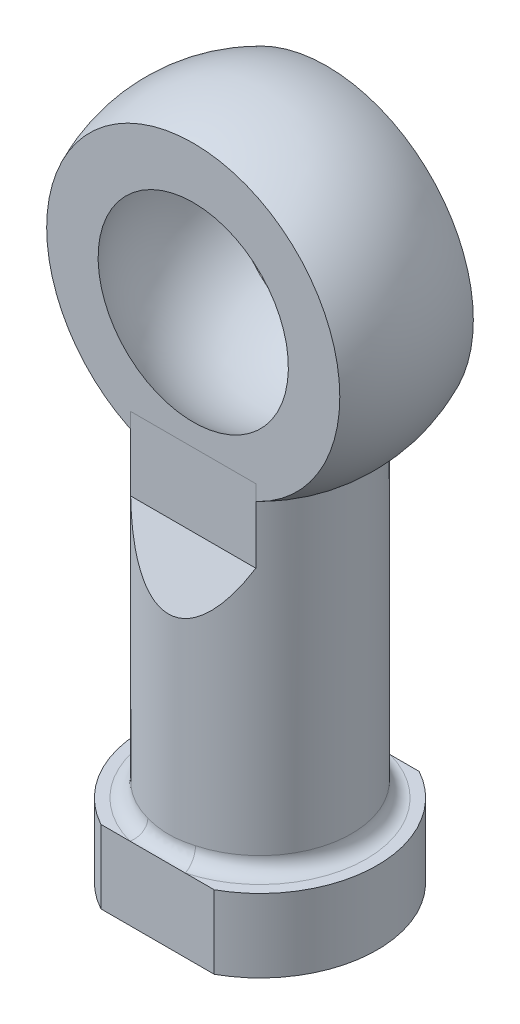
SolidWorks part; units mm, degrees
material "Plain Carbon Steel"
ref_plane "Front Plane" through (0, 0, 0) normal (0, 0, 1) x (1, 0, 0)
ref_plane "Top Plane" through (0, 0, 0) normal (0, 1, 0) x (1, 0, 0)
ref_plane "Right Plane" through (0, 0, 0) normal (1, 0, 0) x (0, 0, -1)
sketch "Sketch2" plane through (0, 0, 0) normal (1, 0, 0) x (0, 0, -1)
  line L0 (0, 15.4744) -> (0, -15.7624) construction
  line L1 (0, 7.938) -> (0, -7.938)
  arc A0 (0, 7.938) -> (0, -7.938) centre (0, 0) cw
  point P6 (0, -14.2606)
  dimension "D1" = 7.938
sketch "Sketch3" plane through (0, 0, 0) normal (1, 0, 0) x (0, 0, -1)
  line L0 (-8.1466, 0) -> (8.1466, 0) construction
  line L1 (0, 31.115) -> (0, -31.115) construction
  line L2 (-4.56, 10.0103) -> (-4.56, 0)
  line L3 (-4.56, 0) -> (4.56, 0)
  line L4 (4.56, 0) -> (4.56, 10.0103)
  arc A0 (-4.56, 10.0103) -> (4.56, 10.0103) centre (0, 0) cw
  point P8 (0, 11)
  dimension "D2" = 9.12
  dimension "D1" = 11
revolve "Revolve2" add sketch "Sketch3"
revolve "Cut-Revolve2" cut sketch "Sketch2" angle 360 about L0
sketch "Sketch4" plane through (0, 0, 0) normal (1, 0, 0) x (0, 0, -1)
  line L0 (0, -11) -> (0, -35.6534) construction
  arc A0 (-4.56, -10.0103) -> (4.56, -10.0103) centre (0, 0) ccw construction
ref_plane "Plane1" through (0, -11, 0) normal (0, 1, 0) x (-1, 0, 0)
sketch "Sketch5" plane through (0, -11, 0) normal (0, 1, 0) x (-1, 0, 0)
  circle A0 centre (0, 0) radius 6.25
  circle A1 centre (0, 0) radius 3.4
  dimension "D1" = 12.5
  dimension "D2" = 6.8
extrude "Extrude2" add sketch "Sketch5" against normal blind 25 and the other way blind 3 separate body
cosmetic thread "Cosmetic Thread1" parameters "D1"=29, "D2"=8
sketch "Sketch7" plane through (0, -36, 0) normal (0, -1, 0) x (1, 0, 0)
  line L0 (-3.873, 7) -> (3.873, 7)
  line L1 (-3.873, -7) -> (3.873, -7)
  circle A0 centre (0, 0) radius 3.4 construction
  circle A1 centre (0, 0) radius 3.4
  arc A2 (-3.873, 7) -> (-3.873, -7) centre (0, 0) ccw
  arc A3 (3.873, -7) -> (3.873, 7) centre (0, 0) ccw
  dimension "D1" = 16
  dimension "D2" = 14
extrude "Boss-Extrude1" add sketch "Sketch7" against normal blind 5
sketch "Sketch6" plane through (0, 0, 0) normal (1, 0, 0) x (0, 0, -1)
  line L0 (0, 18.0632) -> (0, -54.6469) construction
  line L1 (10.0987, 0) -> (-10.0987, 0) construction
  line L2 (0, -11) -> (0, -35.6534) construction
  point P5 (0, 0)
  point P6 (0, -15)
fillet "Fillet1" radius 1 1 edges at (0, -31, -6.25)
sketch "Sketch8" plane through (0, 0, 0) normal (1, 0, 0) x (0, 0, -1)
  line L0 (0, 0) -> (0, -37.9096) construction
  line L1 (-4.56, 0) -> (-4.56, -13)
  line L2 (-4.56, 10.0103) -> (-4.56, -10.0103) construction
  line L3 (-4.56, -13) -> (-6.25, -17)
  line L4 (-6.25, -8) -> (-6.25, -30.0318) construction
  line L5 (-6.25, -17) -> (-14.3389, -17)
  line L6 (-14.3389, -17) -> (-14.3389, 16.9811)
  line L7 (-14.3389, 16.9811) -> (14.3389, 16.9811)
  line L8 (-4.56, 0) -> (-4.56, 14.7187)
  line L9 (-4.56, 14.7187) -> (4.56, 14.7187)
  line L10 (4.56, 0) -> (4.56, 14.7187)
  line L11 (4.56, 0) -> (4.56, -13)
  line L12 (4.56, -13) -> (6.25, -17)
  line L13 (6.25, -17) -> (14.3389, -17)
  line L14 (14.3389, -17) -> (14.3389, 16.9811)
  point P16 (0, 14.7187)
  point P21 (0, 16.9811)
  dimension "D1" = 13
  dimension "D2" = 4
extrude "Cut-Extrude1" cut sketch "Sketch8" against normal through all and the other way through all
